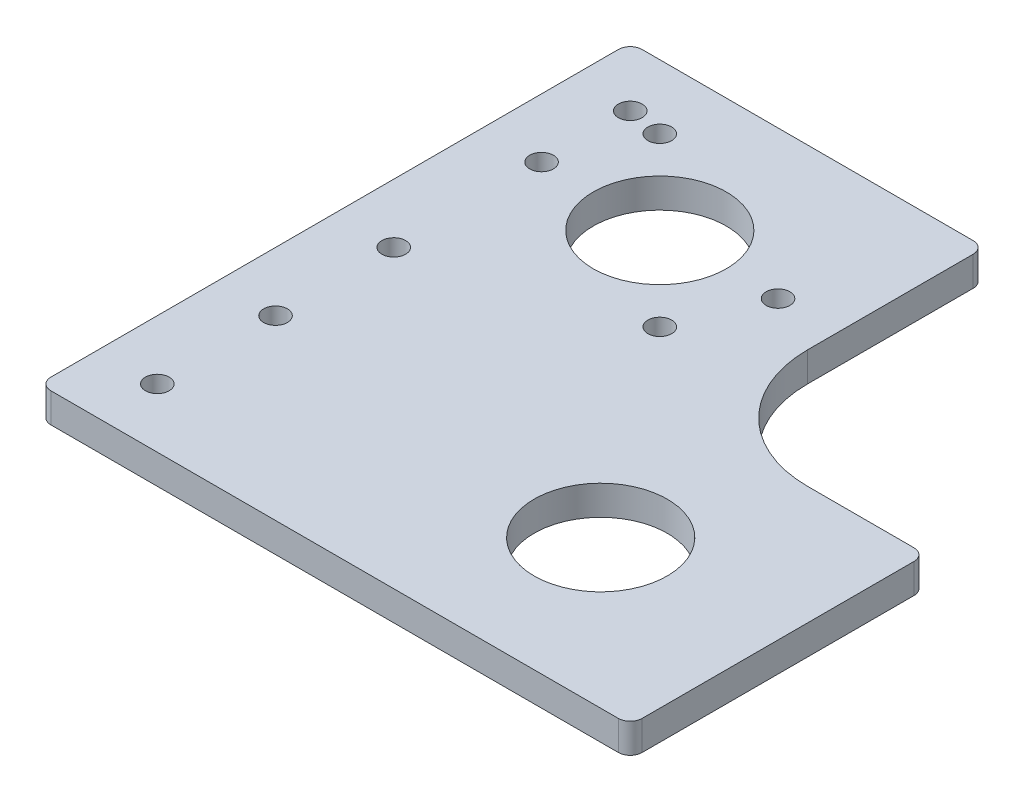
SolidWorks part; units mm, degrees
ref_plane "Front Plane" through (0, 0, 0) normal (0, 0, 1) x (1, 0, 0)
ref_plane "Top Plane" through (0, 0, 0) normal (0, 1, 0) x (1, 0, 0)
ref_plane "Right Plane" through (0, 0, 0) normal (1, 0, 0) x (0, 0, -1)
sketch "Sketch1" plane through (0, 0, 0) normal (0, 1, 0) x (1, 0, 0)
  line L1 (0, 0) -> (-127, 0)
  line L2 (0, 0) -> (0, 127)
  line L3 (0, 127) -> (-127, 127)
  line L4 (-127, 0) -> (-127, 127)
  dimension "D1" = 127
  dimension "D2" = 127
extrude "Boss-Extrude1" add sketch "Sketch1" along normal blind 6.35
sketch "Sketch2" plane through (0, 6.35, 0) normal (0, 1, 0) x (1, 0, 0)
  line L0 (0, 127) -> (-127, 127) construction
  line L1 (0, 127) -> (-50.8, 127)
  line L2 (0, 127) -> (0, 63.5)
  line L3 (0, 63.5) -> (-50.8, 63.5)
  line L4 (-50.8, 127) -> (-50.8, 63.5)
  line L5 (0, 0) -> (0, 127) construction
  dimension "D1" = 0
  dimension "D2" = 50.8
  dimension "D3" = 63.5
extrude "Cut-Extrude1" cut sketch "Sketch2" against normal through all
sketch "Sketch3" plane through (0, 6.35, 0) normal (0, 1, 0) x (1, 0, 0)
  line L0 (0, 0) -> (0, 63.5) construction
  line L1 (-50.8, 63.5) -> (0, 63.5) construction
  circle A0 centre (-38.1, 31.75) radius 14.3002
  dimension "D1" = 28.6004
  dimension "D2" = 38.1
  dimension "D3" = 31.75
extrude "Cut-Extrude2" cut sketch "Sketch3" against normal through all
sketch "Sketch4" plane through (0, 6.35, 0) normal (0, 1, 0) x (1, 0, 0)
  line L0 (-50.8, 127) -> (-127, 127) construction
  line L2 (-127, 127) -> (-127, 0) construction
  circle A0 centre (-88.9, 95.25) radius 25.4
  dimension "D1" = 50.8
  dimension "D2" = 31.75
  dimension "D4" = 38.1
sketch "Sketch5" plane through (0, 6.35, 0) normal (0, 1, 0) x (1, 0, 0)
  circle A0 centre (-114.3, 95.25) radius 2.5527
  circle A1 centre (-88.9, 95.25) radius 25.4 construction
  dimension "D1" = 5.1054
  dimension "D2" = 25.4
extrude "Cut-Extrude4" cut sketch "Sketch5" against normal through all
ref_axis "Axis1" through (-88.9, 6.35, -95.25) along (0, 1, 0)
pattern_circular "CirPattern1" count 8 every 45 about axis through (-88.9, 6.35, -95.25) along (0, 1, 0) skipping 1, 2, 5, 6 of "Cut-Extrude4"
sketch "Sketch6" plane through (0, 6.35, 0) normal (0, 1, 0) x (1, 0, 0)
  circle A0 centre (-88.9, 95.25) radius 14.3002
  dimension "D1" = 28.6004
extrude "Cut-Extrude5" cut sketch "Sketch6" against normal through all
fillet "Fillet1" radius 2.54 5 edges at (-127, 3.175, 0) (0, 3.175, 0) (0, 3.175, -63.5) (-50.8, 3.175, -127) (-127, 3.175, -127)
fillet "Fillet2" radius 25.4 1 edges at (-50.8, 3.175, -63.5)
sketch "Sketch10" plane through (0, 6.35, 0) normal (0, 1, 0) x (1, 0, 0)
  line L0 (-127, 124.46) -> (-127, 2.54) construction
  line L1 (-124.46, 0) -> (-2.54, 0) construction
  circle A0 centre (-114.3, 12.7) radius 2.5527
  dimension "D1" = 5.1054
  dimension "D2" = 12.7
  dimension "D3" = 12.7
extrude "Cut-Extrude7" cut sketch "Sketch10" against normal through all
pattern_linear "LPattern1" count 5 spacing 25.4 along (0, 0, -1) skipping (3, 0) of "Cut-Extrude7"
